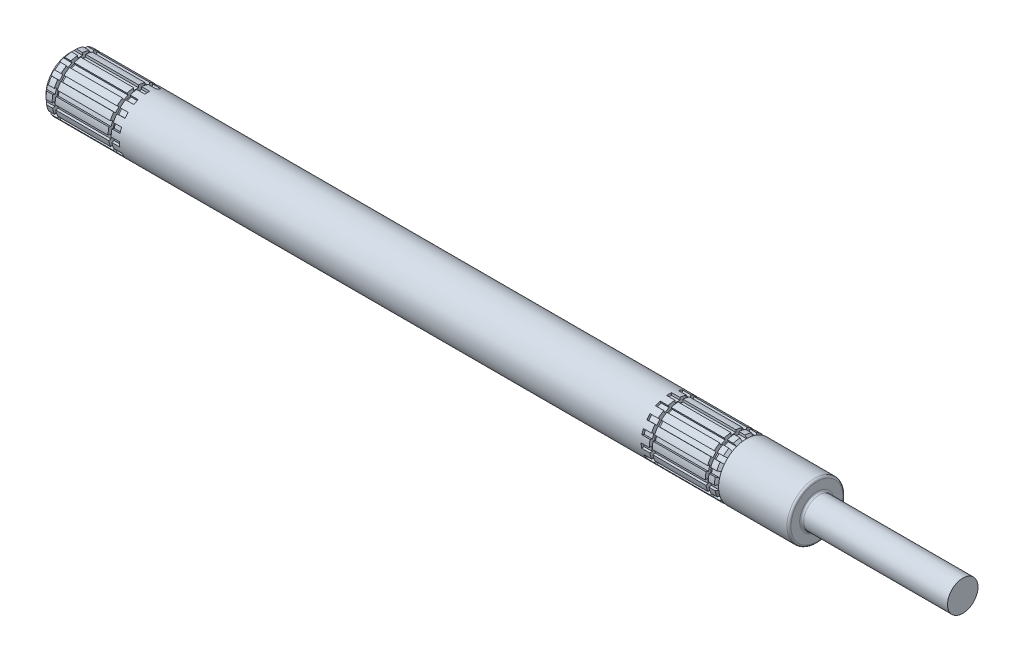
SolidWorks part; units mm, degrees
material "AISI 4130 Steel, annealed at 865C"
ref_plane "Front Plane" through (0, 0, 0) normal (0, 0, 1) x (1, 0, 0)
ref_plane "Top Plane" through (0, 0, 0) normal (0, 1, 0) x (1, 0, 0)
ref_plane "Right Plane" through (0, 0, 0) normal (1, 0, 0) x (0, 0, -1)
sketch "Sketch1" plane through (0, 0, 0) normal (0, 0, 1) x (1, 0, 0)
  line L0 (0, 0) -> (332.1663, 0)
  line L1 (0, 0) -> (0, 13.75)
  line L2 (0, 13.75) -> (5, 13.75)
  line L3 (5, 13.75) -> (5, 11.25)
  line L4 (5, 11.25) -> (6.5, 11.25)
  line L5 (6.5, 11.25) -> (6.5, 13.75)
  line L6 (6.5, 13.75) -> (32.5, 13.75)
  line L7 (32.5, 13.75) -> (32.5, 11.25)
  line L8 (32.5, 11.25) -> (34, 11.25)
  line L9 (34, 11.25) -> (34, 13.75)
  line L10 (34, 13.75) -> (298.1663, 13.75)
  line L11 (332.1663, 13.75) -> (332.1663, 0)
  line L12 (166.0831, 0) -> (166.0831, 13.75) construction
  line L13 (298.1663, 11.25) -> (298.1663, 13.75)
  line L14 (299.6663, 11.25) -> (298.1663, 11.25)
  line L15 (299.6663, 13.75) -> (299.6663, 11.25)
  line L16 (325.6663, 11.25) -> (325.6663, 13.75)
  line L17 (327.1663, 11.25) -> (325.6663, 11.25)
  line L18 (327.1663, 13.75) -> (327.1663, 11.25)
  line L19 (299.6663, 13.75) -> (325.6663, 13.75)
  line L20 (327.1663, 13.75) -> (332.1663, 13.75)
  dimension "D1" = 332.1663
  dimension "D2" = 13.75
  dimension "D3" = 5
  dimension "D4" = 2.5
  dimension "D5" = 1.5
  dimension "D6" = 2.5
  dimension "D7" = 1.5
  dimension "D8" = 26
revolve "Revolve1" add sketch "Sketch1" angle 360 about L0
chamfer "Chamfer1" distance 2 angle 45 2 edges at (0, 0, 13.75) (332.1663, 0, 13.75)
ref_plane "Plane3" through (166.0831, 0, 0) normal (-1, 0, 0) x (0, 0, 1)
sketch "Sketch2" plane through (0, 0, 0) normal (-1, 0, 0) x (0, 0, 1)
  line L0 (0, 0) -> (0, 13.75) construction
  line L1 (1.2, 12.5) -> (-1.2, 12.5)
  line L2 (-1.2, 12.5) -> (-1.2, 14.5)
  line L3 (-1.2, 14.5) -> (0, 14.5)
  line L4 (1.2, 14.5) -> (0, 14.5)
  line L5 (1.2, 12.5) -> (1.2, 14.5)
  circle A0 centre (0, 0) radius 13.75 construction
  point P13 (0, 12.5)
  dimension "D1" = 2
  dimension "D2" = 12.5
  dimension "D3" = 1.2
  dimension "D4" = 2.4
extrude "Cut-Extrude1" cut sketch "Sketch2" against normal blind 38
pattern_circular "CirPattern1" count 15 over 360 about axis through (0, 0, 0) along (-1, 0, 0) of "Cut-Extrude1"
ref_plane "Plane4" through (166.0831, 0, 0) normal (-1, 0, 0) x (0, 0, 1)
mirror "Mirror1" about plane through (166.0831, 0, 0) normal (-1, 0, 0) of "CirPattern1"
sketch "Sketch6" plane through (0, 0, 0) normal (0, 0, 1) x (1, 0, 0)
  line L0 (332.1663, 13.75) -> (366.7063, 13.75)
  line L2 (332.1663, 13.75) -> (332.1663, 0)
  line L3 (332.1663, -11.75) -> (332.1663, 11.75) construction
  line L5 (366.7063, 13.75) -> (366.7063, 7.5)
  line L6 (366.7063, 7.5) -> (438.2763, 7.5)
  line L7 (438.2763, 7.5) -> (438.2763, 0)
  line L9 (300, 0) -> (432.9846, 0) construction
  line L10 (332.1663, 0) -> (438.2763, 0)
  dimension "D1" = 34.54
  dimension "D2" = 13.75
  dimension "D3" = 7.5
  dimension "D4" = 71.57
revolve "Revolve4" add sketch "Sketch6" angle 360 about L10
fillet "Fillet2" radius 0.5 1 edges at (332.1663, 0, 11.75)
fillet "Fillet4" radius 1 2 edges at (366.7063, 0, 7.5) (366.7063, 0, 13.75)
